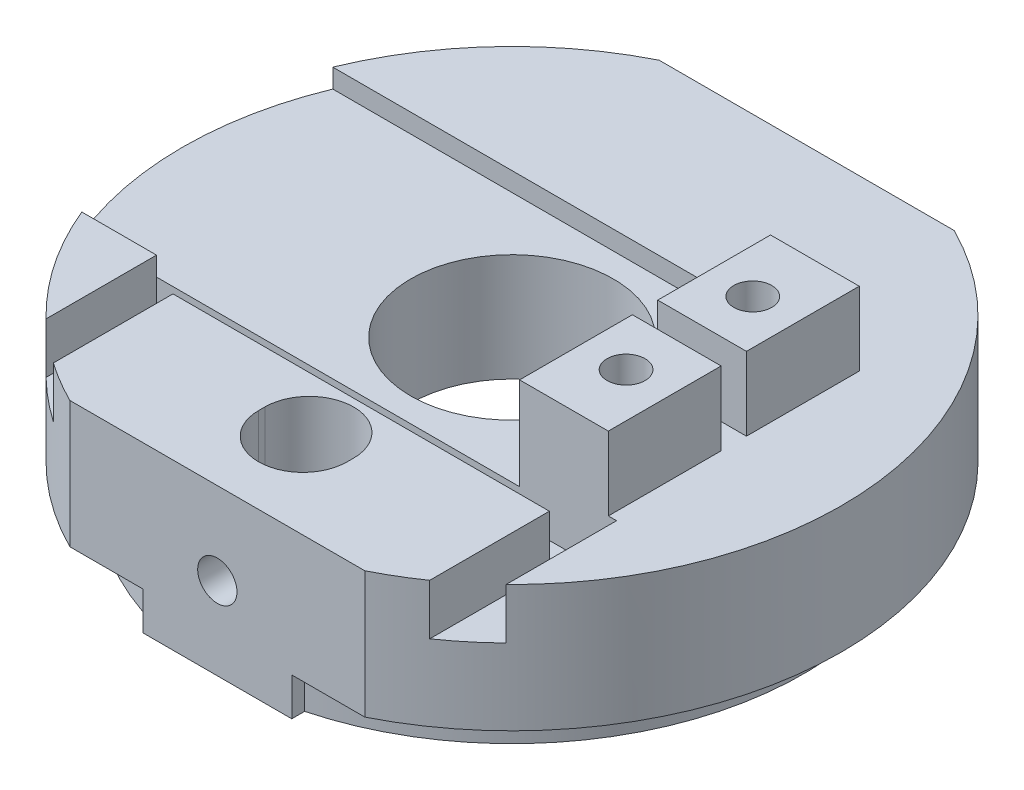
SolidWorks part; units mm, degrees
ref_plane "Front Plane" through (0, 0, 0) normal (0, 0, 1) x (1, 0, 0)
ref_plane "Top Plane" through (0, 0, 0) normal (0, 1, 0) x (1, 0, 0)
ref_plane "Right Plane" through (0, 0, 0) normal (1, 0, 0) x (0, 0, -1)
sketch "Sketch1" plane through (0, 0, 0) normal (0, 1, 0) x (1, 0, 0)
  line L0 (0, -16) -> (0, -16.5) construction
  line L5 (3.5, -16) -> (3.5, -16.5)
  line L6 (-3.5, -16) -> (-3.5, -16.5)
  line L7 (0, -12.5) -> (0, -8) construction
  line L8 (0, 26) -> (0, 23) construction
  line L9 (-17.5, -26) -> (17.5, -26)
  line L10 (-17.5, -26) -> (-17.5, -23.25)
  line L11 (-17.5, -23.25) -> (17.5, -23.25)
  line L12 (17.5, -26) -> (17.5, -23.25)
  line L13 (5.8745, -23.25) -> (-5.8745, -23.25)
  line L14 (5.8745, -23.25) -> (5.8745, -22.2371)
  line L15 (5.8745, -22.2371) -> (-5.8745, -22.2371)
  line L16 (-5.8745, -23.25) -> (-5.8745, -22.2371)
  line L17 (0, 21) -> (0, 23) construction
  line L18 (17.5, 26) -> (-17.5, 26)
  line L19 (17.5, 26) -> (17.5, 23.25)
  line L20 (17.5, 23.25) -> (-17.5, 23.25)
  line L21 (-17.5, 26) -> (-17.5, 23.25)
  circle A0 centre (0, 0) radius 8
  circle A1 centre (0, 0) radius 26
  circle A2 centre (0, 0) radius 23
  circle A3 centre (0, 0) radius 21
  arc A4 (3.5, -16) -> (-3.5, -16) centre (0, -16) ccw
  arc A5 (-3.5, -16.5) -> (3.5, -16.5) centre (0, -16.5) ccw
  circle A6 centre (0, 0) radius 20.75 construction
  circle A7 centre (0, 0) radius 14.5 construction
  point P12 (0, -16.25)
  point P17 (0, -12.5)
  point P18 (0, -20)
  point P23 (0, -26)
  point P24 (0, -22.2371)
  point P37 (0, 0)
  dimension "D1" = 16
  dimension "D2" = 52
  dimension "D3" = 46
  dimension "D4" = 2
  dimension "D5" = 3.5
  dimension "D8" = 41.5
  dimension "D9" = 29
  dimension "D6" = 7.5
  dimension "D7" = 4.5
  dimension "D10" = 35
  dimension "D11" = 23.25
  dimension "D12" = 11.749
extrude "Boss-Extrude1" add sketch "Sketch1" along normal blind 10 contours A2 L9 A1 | L9 A2 A3 | A3 A5 L6 A4 L5 A0 | L15 A2 | A2 L16 L11 region at (-25.3024, 0, 0) region at (-5.7566, 0, 22.7436) region at (-13.64, 0, -17.7113) region at (0, 0, 22.5427) region at (-20.406, 0, 0)
extrude "Boss-Extrude2" add sketch "Sketch1<3>" against normal blind 3 contours L9 A2 A3 | A2 L13 L14 | A2 L15 region at (-5.7566, 0, 22.7436) region at (-13.64, 0, -17.7113) region at (0, 0, 22.5427)
sketch "Sketch1<3>" plane through (0, 0, 0) normal (0, 1, 0) x (1, 0, 0) same geometry as "Sketch1"
sketch "Sketch2" plane through (0, 10, 0) normal (0, 1, 0) x (1, 0, 0)
  line L0 (0, -9.9) -> (0, -12.5) construction
  line L5 (-18.15, -23.25) -> (18.15, -23.25)
  line L6 (-18.15, -23.25) -> (-18.15, -9.9)
  line L7 (-18.15, -9.9) -> (18.15, -9.9)
  line L8 (18.15, -23.25) -> (18.15, -9.9)
  line L10 (-14.85, -23.25) -> (-14.85, -11.9)
  line L11 (-14.85, -11.9) -> (14.85, -11.9)
  line L12 (14.85, -11.9) -> (14.85, -23.25)
  line L13 (-14.85, -11.9) -> (-18.15, -11.9) construction
  line L14 (14.85, -11.9) -> (18.15, -11.9) construction
  line L15 (14.85, -11.9) -> (14.85, -9.9) construction
  line L16 (-11.6378, -23.25) -> (11.6378, -23.25) construction
  line L17 (24.0414, -9.9) -> (-24.0414, -9.9) construction
  arc A0 (3.5, -16) -> (-3.5, -16) centre (0, -16) ccw construction
  arc A1 (11.6378, -23.25) -> (11.6378, 23.25) centre (0, 0) ccw construction
  arc A2 (-11.6378, 23.25) -> (-11.6378, -23.25) centre (0, 0) ccw construction
  point P3 (0, -11.9)
  point P10 (-16.5, -11.9)
  point P21 (16.5, -11.9)
  point P22 (14.85, -10.9)
  dimension "D1" = 3.3
  dimension "D2" = 2
  dimension "D3" = 33
  dimension "D4" = 12.35
  dimension "D5" = 9.9
extrude "Cut-Extrude1" cut sketch "Sketch2" against normal blind 4 contours L11 L12 L8 L7 L6 L10 region at (-17.7632, 10, 16.575)
sketch "Sketch3" plane through (0, 10, 0) normal (0, 1, 0) x (1, 0, 0)
  line L1 (-26, 9.9) -> (10.5, 9.9)
  line L2 (-26, 9.9) -> (-26, -9.9)
  line L3 (-26, -9.9) -> (10.5, -9.9)
  line L4 (10.5, 9.9) -> (10.5, -9.9)
  arc A0 (18.15, -18.6166) -> (11.6378, 23.25) centre (0, 0) ccw construction
  point P4 (10.5, 0)
  dimension "D1" = 19.8
  dimension "D2" = 10.5
extrude "Cut-Extrude2" cut sketch "Sketch3" against normal blind 1.5
sketch "Sketch4" plane through (0, 10, 0) normal (0, 1, 0) x (1, 0, 0)
  line L0 (14, 5) -> (14, -5) construction
  line L1 (10.5, 9.9) -> (17.5, 9.9)
  line L2 (10.5, 9.9) -> (10.5, 1)
  line L3 (10.5, 1) -> (17.5, 1)
  line L4 (17.5, 9.9) -> (17.5, 1)
  line L5 (10.5, -9.9) -> (17.5, -9.9)
  line L6 (10.5, -9.9) -> (10.5, -1)
  line L7 (10.5, -1) -> (17.5, -1)
  line L8 (17.5, -9.9) -> (17.5, -1)
  line L9 (10.5, -9.9) -> (10.5, 9.9) construction
  line L10 (10.5, -9.9) -> (10.5, 9.9) construction
  line L11 (-24.0414, -9.9) -> (-18.15, -9.9) construction
  circle A0 centre (14, 5) radius 1.5
  circle A1 centre (14, -5) radius 1.5
  point P9 (0, 0)
  point P14 (14, 0)
  point P15 (0, 0)
  point P16 (14, -9.9)
  point P20 (10.5, 0)
  dimension "D2" = 10
  dimension "D3" = 3
  dimension "D1" = 2
  dimension "D4" = 3.5
extrude "Boss-Extrude3" add sketch "Sketch4" along normal blind 5.8
sketch "Sketch5" plane through (0, 0, 23.25) normal (0, 0, 1) x (1, 0, 0)
  line L0 (18.15, 6) -> (14.85, 6) construction
  circle A0 centre (0, 3.5) radius 1.55
  dimension "D1" = 3.1
  dimension "D2" = 2.5
extrude "Cut-Extrude3" cut sketch "Sketch5" against normal blind 6
